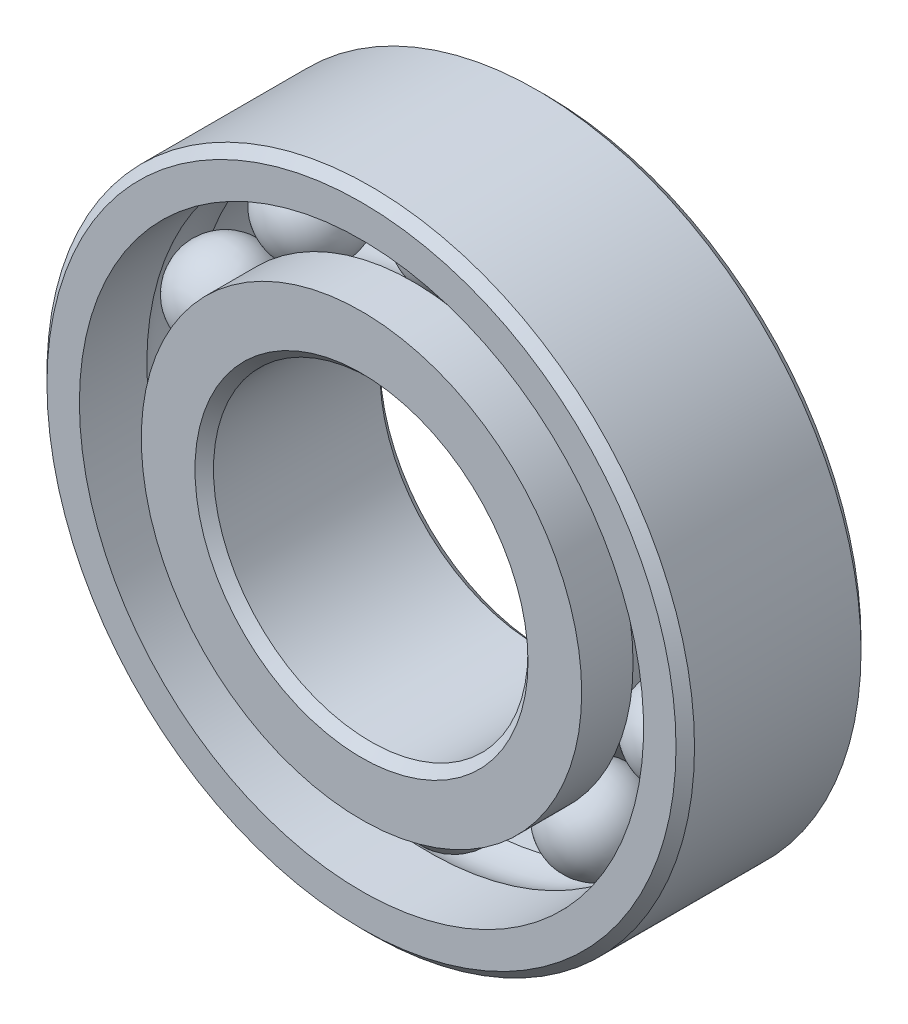
SolidWorks part; units mm, degrees
ref_plane "Front Plane" through (0, 0, 0) normal (0, 0, 1) x (1, 0, 0)
ref_plane "Top Plane" through (0, 0, 0) normal (0, 1, 0) x (1, 0, 0)
ref_plane "Right Plane" through (0, 0, 0) normal (1, 0, 0) x (0, 0, -1)
sketch "Sketch1" plane through (0, 0, 0) normal (1, 0, 0) x (0, 0, -1)
  line L0 (-5, 0) -> (5, 0) construction
  line L1 (0, 17.5) -> (0, -17.5) construction
  line L2 (4.5, 17.5) -> (-4.5, 17.5)
  line L3 (-4.5, 17.5) -> (-5, 17)
  line L8 (4.5, 17.5) -> (5, 17)
  line L9 (0, 17.5) -> (0, 13) construction
  line L10 (0, 13) -> (0, 8.5) construction
  line L11 (-5, 17) -> (5, 17)
  point P14 (0, 8.5)
  dimension "Width" = 10
  dimension "OD" = 35
  dimension "D2" = 0.5
  dimension "Shaft Dia" = 17
  dimension "D5" = 0.5
revolve "Revolve1" add sketch "Sketch1" angle 360 about L0
ref_plane "Plane1" through (0, 0, 0) normal (1, 0, 0) x (0, 0, -1)
sketch "Sketch6" plane through (0, 0, 0) normal (1, 0, 0) x (0, 0, -1)
  line L0 (-5, 11.9011) -> (-2.2222, 11.9011)
  line L2 (-5, 0) -> (5, 0) construction
  line L3 (-5, 9) -> (-5, 11.9011)
  line L5 (-5, 9) -> (-4.5, 8.5)
  line L6 (-4.5, 8.5) -> (4.5, 8.5)
  line L8 (4.5, 8.5) -> (5, 9)
  line L10 (5, 9) -> (5, 11.9011)
  line L11 (5, 11.9011) -> (2.2222, 11.9011)
  arc A2 (-2.2222, 11.9011) -> (2.2222, 11.9011) centre (0, 13) ccw
revolve "Revolve9" add sketch "Sketch6" angle 360 about L2
sketch "Sketch4" plane through (0, 0, 0) normal (1, 0, 0) x (0, 0, -1)
  line L0 (-2.4791, 13) -> (2.4791, 13)
  arc A0 (2.4791, 13) -> (-2.4791, 13) centre (0, 13) ccw
revolve "Revolve4" add sketch "Sketch4" angle 360 about L0
ref_axis "Axis1" through (0, 0, -5) along (0, 0, 1)
pattern_circular "CirPattern1" count 10 over 360 about axis through (0, 0, -5) along (0, 0, 1) of bodies 104
ref_plane "Plane2" through (0, 0, 0) normal (1, 0, 0) x (0, 0, -1)
sketch "Sketch7" plane through (0, 0, 0) normal (1, 0, 0) x (0, 0, -1)
  line L0 (5, 17) -> (5, -17) construction
  line L1 (5, 0) -> (-5, 0) construction
  line L2 (1.2116, 15.2469) -> (5, 15.2469)
  line L13 (-5, 17) -> (5, 17)
  line L14 (5, 17) -> (5, 15.2469)
  line L16 (-5, 17) -> (-5, 15.2469)
  line L19 (-5, 15.2469) -> (-1.3562, 15.2469)
  arc A0 (1.2116, 15.2469) -> (-1.3562, 15.2469) centre (-0.0723, 13.1251) ccw
  point P18 (-4.75, 17.25)
  dimension "D1" = 1.7531
revolve "Revolve11" add sketch "Sketch7" angle 360 about L1
